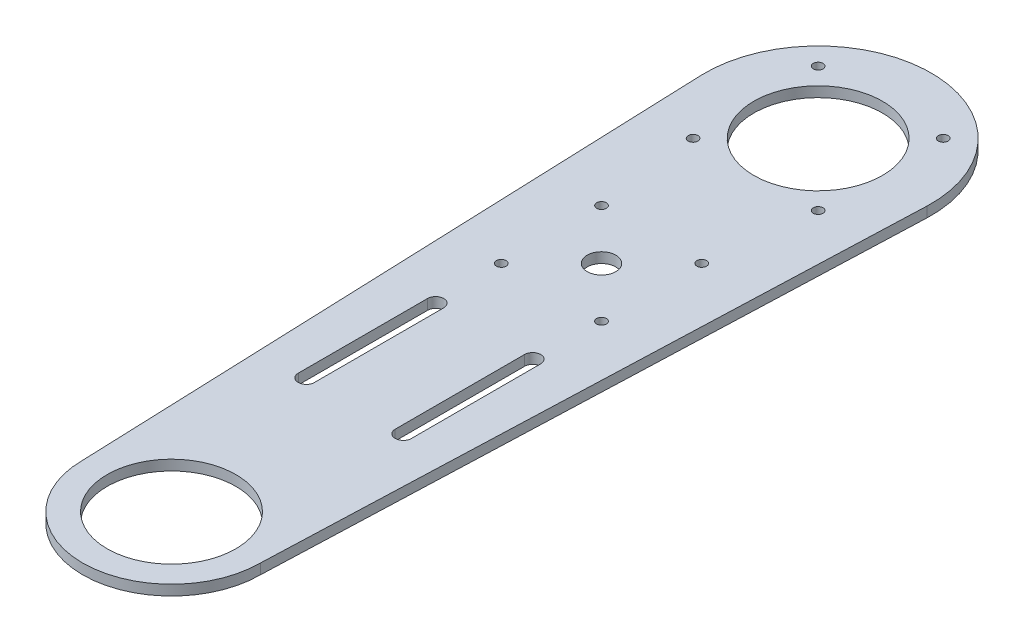
SolidWorks part; units mm, degrees
ref_plane "Front Plane" through (0, 0, 0) normal (0, 0, 1) x (1, 0, 0)
ref_plane "Top Plane" through (0, 0, 0) normal (0, 1, 0) x (1, 0, 0)
ref_plane "Right Plane" through (0, 0, 0) normal (1, 0, 0) x (0, 0, -1)
sketch "Sketch1" plane through (0, 0, 0) normal (0, 1, 0) x (1, 0, 0)
  line L0 (-27.5, -100) -> (-34.9753, 98.6841)
  line L1 (27.5, -100) -> (34.9753, 98.6841)
  arc A0 (-27.5, -100) -> (27.5, -100) centre (0, -100) ccw
  arc A2 (34.9753, 98.6841) -> (-34.9753, 98.6841) centre (0, 100) ccw
  dimension "D1" = 55
  dimension "D2" = 200
  dimension "D3" = 70
  dimension "D4" = 100
extrude "Boss-Extrude1" add sketch "Sketch1" along normal blind 3.175 contours A0 | A0 region at (0, 0, -8.8693)
sketch "Sketch2" plane through (0, 3.175, 0) normal (0, 1, 0) x (1, 0, 0)
  circle A0 centre (0, -100) radius 19.9
  circle A1 centre (0, 100) radius 19.9
  dimension "D1" = 39.8
  dimension "D2" = 200
  dimension "D3" = 100
extrude "Cut-Extrude1" cut sketch "Sketch2" against normal through all
sketch "Esquisse1" plane through (0, 3.175, 0) normal (0, 1, 0) x (1, 0, 0)
  circle A0 centre (0, 100) radius 27.35
  circle A2 centre (0, 100) radius 19.9 construction
  dimension "D1" = 54.7
sketch "Esquisse2" plane through (0, 3.175, 0) normal (0, 1, 0) x (1, 0, 0)
  line L0 (-19.3394, 80.6606) -> (19.3394, 80.6606) construction
  line L1 (19.3394, 80.6606) -> (19.3394, 119.3394) construction
  line L2 (19.3394, 119.3394) -> (-19.3394, 119.3394) construction
  line L3 (-19.3394, 119.3394) -> (-19.3394, 80.6606) construction
  circle A0 centre (19.3394, 80.6606) radius 1.5
  circle A2 centre (19.3394, 119.3394) radius 1.5
  circle A3 centre (-19.3394, 119.3394) radius 1.5
  circle A4 centre (-19.3394, 80.6606) radius 1.5
  circle A6 centre (0, 100) radius 27.35 construction
  point P2 (0, 80.6606)
  dimension "D1" = 3
extrude "Enlèv. mat.-Extru.1" cut sketch "Esquisse2" against normal through all
sketch "Sketch3" plane through (0, 3.175, 0) normal (0, 1, 0) x (1, 0, 0)
  circle A0 centre (0, 33) radius 4.425
  dimension "D1" = 8.85
extrude "Cut-Extrude2" cut sketch "Sketch3" against normal through all
sketch "Sketch5" plane through (0, 3.175, 0) normal (0, 1, 0) x (1, 0, 0)
  line L0 (-17.5, -43.3) -> (-17.5, -3.3)
  line L1 (-12.5, -3.3) -> (-12.5, -43.3)
  line L2 (12.5, -43.3) -> (12.5, -3.3)
  line L3 (17.5, -3.3) -> (17.5, -43.3)
  arc A0 (-17.5, -3.3) -> (-12.5, -3.3) centre (-15, -3.3) cw
  arc A1 (-12.5, -43.3) -> (-17.5, -43.3) centre (-15, -43.3) cw
  arc A2 (12.5, -3.3) -> (17.5, -3.3) centre (15, -3.3) cw
  arc A3 (17.5, -43.3) -> (12.5, -43.3) centre (15, -43.3) cw
extrude "Cut-Extrude4" cut sketch "Sketch5" against normal through all
sketch "Sketch6" plane through (0, 0, 0) normal (0, -1, 0) x (-1, 0, 0)
  circle A0 centre (15.5, 17.5) radius 1.5
  circle A1 centre (-15.5, 17.5) radius 1.5
  circle A2 centre (-15.5, 48.5) radius 1.5
  circle A3 centre (15.5, 48.5) radius 1.5
  circle A4 centre (15.5, 48.5) radius 1.5 construction
extrude "Cut-Extrude5" cut sketch "Sketch6" against normal through all
